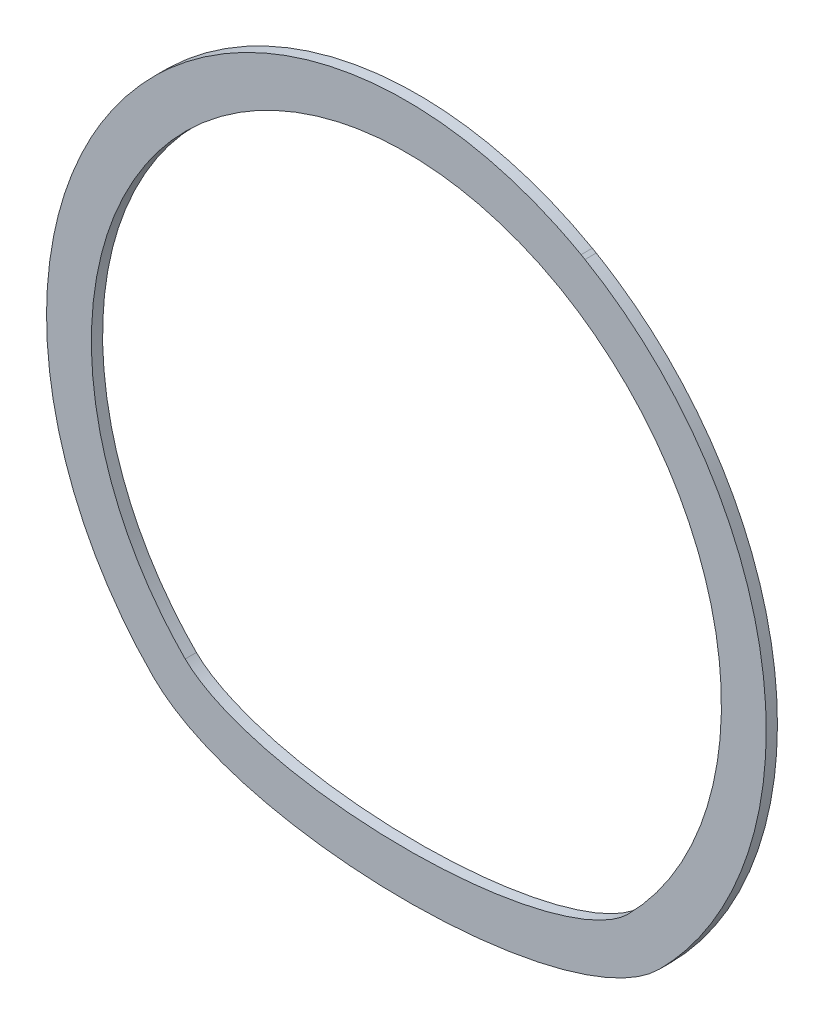
SolidWorks part; units mm, degrees
material "Balsa"
ref_plane "Front Plane" through (0, 0, 0) normal (0, 0, 1) x (1, 0, 0)
ref_plane "Top Plane" through (0, 0, 0) normal (0, 1, 0) x (1, 0, 0)
ref_plane "Right Plane" through (0, 0, 0) normal (1, 0, 0) x (0, 0, -1)
sketch "Sketch2" plane through (0, 0, 0) normal (0, 0, 1) x (1, 0, 0)
  spline S0 degree 3 poles (1916.9359, -3331.6619) (-3240.6007, 2836.854) (4021.1791, -1543.6671) (-3851.7215, 176.6002) knots -506.110745 -506.110745 -506.110745 -506.110745 508.578658 508.578658 508.578658 508.578658 only from (49.5009, 91.348) to (50.6103, 90.7129)
  spline S1 degree 3 poles (2660.8438, -2993.62) (-94.0194, -31.8616) (-51.8415, -94.056) (-74.4696, -70.0026) (-75.8372, -68.488) (-77.1861, -66.9319) (-78.5157, -65.3347) (-79.8244, -63.6962) (-81.5476, -61.4464) (-83.6416, -58.5297) (-85.6296, -55.5014) (-87.1622, -52.9973) (-88.2859, -51.0701) (-90.1147, -47.7724) (-92.5499, -42.8914) (-95.3516, -36.1752) (-97.8068, -28.8548) (-99.4166, -22.4927) (-100.4844, -16.9735) (-101.2174, -12.1158) (-101.8059, -6.1085) (-102.0556, 1.0556) (-101.6376, 11.9166) (-99.5817, 24.7034) (-94.9478, 39.4776) (-88.6565, 52.7081) (-80.0434, 65.5541) (-69.8712, 76.7554) (-58.637, 85.9148) (-47.202, 92.899) (-35.7905, 98.0522) (-24.0008, 101.7167) (-12.0295, 103.8942) (-3.6569, 104.3953) (0.9911, 104.3723) (2.6447, 104.3478) (5.2959, 104.2559) (8.9441, 104.0024) (12.9235, 103.5662) (16.8979, 102.9692) (20.8607, 102.2106) (24.805, 101.2899) (28.7242, 100.207) (32.6113, 98.9619) (36.4593, 97.5551) (39.9429, 96.1186) (42.4433, 94.9816) (43.9946, 94.2376) (44.9225, 93.7809) (45.8466, 93.3143) (46.7667, 92.8378) (47.6827, 92.3514) (68.8529, 80.8443) (140.5977, 30.98) (-3481.9654, 1968.9745) knots -0.290492 -0.290492 -0.290492 -0.290492 0.006795 0.013654 0.020575 0.02756 0.034609 0.041722 0.048899 0.063446 0.078252 0.085753 0.09332 0.100952 0.124124 0.148785 0.174948 0.202627 0.215494 0.232144 0.2526 0.276886 0.305032 0.363116 0.408011 0.462235 0.511576 0.564908 0.615598 0.658549 0.700916 0.742691 0.78387 0.82445 0.827809 0.831171 0.841279 0.854802 0.868378 0.882008 0.895692 0.909428 0.923217 0.93706 0.950955 0.964902 0.975398 0.978902 0.982411 0.985922 0.989437 0.992954 0.996476 1.243806 1.243806 1.243806 1.243806 only from (-71.6774, -72.9104) to (49.5009, 91.348)
  spline S2 degree 3 poles (-71.6774, -72.9104) (-72.1092, -72.4767) (-72.9729, -71.5936) (-74.4696, -70.0026) (-75.8372, -68.488) (-77.1861, -66.9319) (-78.5157, -65.3347) (-79.8244, -63.6962) (-81.5476, -61.4464) (-83.6416, -58.5297) (-85.6296, -55.5014) (-87.1622, -52.9973) (-88.2859, -51.0701) (-90.1147, -47.7724) (-92.5499, -42.8914) (-95.3516, -36.1752) (-97.8068, -28.8548) (-99.4166, -22.4927) (-100.4844, -16.9735) (-101.2174, -12.1158) (-101.8059, -6.1085) (-102.0556, 1.0556) (-101.6376, 11.9166) (-99.5817, 24.7034) (-94.9478, 39.4776) (-88.6565, 52.7081) (-80.0434, 65.5541) (-69.8712, 76.7554) (-58.637, 85.9148) (-47.202, 92.899) (-35.7905, 98.0522) (-24.0008, 101.7167) (-12.0295, 103.8942) (-3.6569, 104.3953) (0.9911, 104.3723) (2.6447, 104.3478) (5.2959, 104.2559) (8.9441, 104.0024) (12.9235, 103.5662) (16.8979, 102.9692) (20.8607, 102.2106) (24.805, 101.2899) (28.7242, 100.207) (32.6113, 98.9619) (36.4593, 97.5551) (39.9429, 96.1186) (42.4433, 94.9816) (43.9946, 94.2376) (44.9225, 93.7809) (45.8466, 93.3143) (46.7667, 92.8378) (47.6827, 92.3514) (48.5618, 91.8735) (49.1883, 91.5244) (49.5009, 91.348) knots 0 0 0 0 0.006795 0.013654 0.020575 0.02756 0.034609 0.041722 0.048899 0.063446 0.078252 0.085753 0.09332 0.100952 0.124124 0.148785 0.174948 0.202627 0.215494 0.232144 0.2526 0.276886 0.305032 0.363116 0.408011 0.462235 0.511576 0.564908 0.615598 0.658549 0.700916 0.742691 0.78387 0.82445 0.827809 0.831171 0.841279 0.854802 0.868378 0.882008 0.895692 0.909428 0.923217 0.93706 0.950955 0.964902 0.975398 0.978902 0.982411 0.985922 0.989437 0.992954 0.996476 1 1 1 1
  spline S3 degree 3 poles (49.5009, 91.348) (49.872, 91.1385) (50.2418, 90.9268) (50.6103, 90.7129) knots 0 0 0 0 1 1 1 1
  spline S4 degree 3 poles (-3346.3837, 2202.0383) (73.8317, 60.8817) (25.255, 106.4505) (53.9325, 88.7036) (55.5798, 87.6387) (57.2181, 86.5331) (58.847, 85.3874) (60.4652, 84.2011) (62.6149, 82.559) (65.2687, 80.4032) (68.3802, 77.661) (71.4204, 74.7537) (74.3792, 71.6812) (77.2464, 68.4441) (79.5428, 65.6199) (81.3243, 63.2803) (82.6352, 61.4798) (83.9151, 59.6395) (85.6826, 56.9767) (87.8969, 53.3695) (90.4626, 48.6769) (92.8892, 43.6261) (95.1327, 38.2157) (97.1465, 32.4482) (98.8821, 26.3306) (100.2892, 19.8751) (101.2586, 13.4739) (101.8173, 7.2467) (102.0152, 1.305) (101.8786, -4.6242) (101.3926, -10.7347) (100.5371, -16.8676) (99.3294, -22.8638) (97.8936, -28.3722) (96.657, -32.2698) (95.7856, -34.7444) (95.046, -36.7643) (93.9532, -39.5358) (92.4358, -43.007) (90.8217, -46.3649) (89.1186, -49.6082) (87.3342, -52.7363) (85.4757, -55.7486) (83.5505, -58.6453) (81.5655, -61.4266) (79.3077, -64.3807) (77.437, -66.6472) (76.0073, -68.2889) (75.2951, -69.0897) (74.579, -69.8782) (73.8594, -70.6545) (73.1363, -71.4184) (60.0474, -84.947) (112.6093, -25.8248) (-2703.3653, -2952.5697) knots -0.468149 -0.468149 -0.468149 -0.468149 0.010157 0.020393 0.030709 0.041103 0.051576 0.062128 0.072758 0.094254 0.116062 0.138181 0.16061 0.183347 0.206391 0.218027 0.22974 0.241529 0.253393 0.280162 0.30828 0.337739 0.36853 0.400644 0.434071 0.4688 0.504821 0.536145 0.567394 0.59857 0.62967 0.664059 0.696204 0.726123 0.75383 0.760691 0.767516 0.787768 0.807688 0.827278 0.84654 0.865477 0.884089 0.902378 0.920346 0.937994 0.961032 0.966703 0.97234 0.977942 0.983508 0.98904 0.994538 1.247123 1.247123 1.247123 1.247123 only from (50.6103, 90.7129) to (71.6784, -72.9104)
  spline S5 degree 3 poles (50.6103, 90.7129) (51.1284, 90.4118) (52.1672, 89.796) (53.9325, 88.7036) (55.5798, 87.6387) (57.2181, 86.5331) (58.847, 85.3874) (60.4652, 84.2011) (62.6149, 82.559) (65.2687, 80.4032) (68.3802, 77.661) (71.4204, 74.7537) (74.3792, 71.6812) (77.2464, 68.4441) (79.5428, 65.6199) (81.3243, 63.2803) (82.6352, 61.4798) (83.9151, 59.6395) (85.6826, 56.9767) (87.8969, 53.3695) (90.4626, 48.6769) (92.8892, 43.6261) (95.1327, 38.2157) (97.1465, 32.4482) (98.8821, 26.3306) (100.2892, 19.8751) (101.2586, 13.4739) (101.8173, 7.2467) (102.0152, 1.305) (101.8786, -4.6242) (101.3926, -10.7347) (100.5371, -16.8676) (99.3294, -22.8638) (97.8936, -28.3722) (96.657, -32.2698) (95.7856, -34.7444) (95.046, -36.7643) (93.9532, -39.5358) (92.4358, -43.007) (90.8217, -46.3649) (89.1186, -49.6082) (87.3342, -52.7363) (85.4757, -55.7486) (83.5505, -58.6453) (81.5655, -61.4266) (79.3077, -64.3807) (77.437, -66.6472) (76.0073, -68.2889) (75.2951, -69.0897) (74.579, -69.8782) (73.8594, -70.6545) (73.1363, -71.4184) (72.3175, -72.2647) (71.8912, -72.6967) (71.6784, -72.9104) knots 0 0 0 0 0.010157 0.020393 0.030709 0.041103 0.051576 0.062128 0.072758 0.094254 0.116062 0.138181 0.16061 0.183347 0.206391 0.218027 0.22974 0.241529 0.253393 0.280162 0.30828 0.337739 0.36853 0.400644 0.434071 0.4688 0.504821 0.536145 0.567394 0.59857 0.62967 0.664059 0.696204 0.726123 0.75383 0.760691 0.767516 0.787768 0.807688 0.827278 0.84654 0.865477 0.884089 0.902378 0.920346 0.937994 0.961032 0.966703 0.97234 0.977942 0.983508 0.98904 0.994538 1 1 1 1
  spline S6 degree 3 poles (-3842.8721, 688.3174) (4597.8502, -352.084) (-4597.8455, -352.0843) (3842.8638, 688.3162) knots -2.698057 -2.698057 -2.698057 -2.698057 3.698055 3.698055 3.698055 3.698055 weights 1 1 1 1 only from (71.6784, -72.9104) to (-71.6774, -72.9104)
  spline S7 degree 3 poles (71.6784, -72.9104) (46.3599, -98.3417) (-46.3589, -98.3417) (-71.6774, -72.9104) knots 0 0 0 0 1 1 1 1 weights 1 1 1 1
  spline S8 degree 1 poles (-62.6772, -63.9502) (43.2582, 80.2883) knots 0 0 1 1 construction
  spline S9 degree 1 poles (43.2582, 80.2883) (44.2327, 79.7303) knots 0 0 1 1 construction
  spline S10 degree 1 poles (44.2327, 79.7303) (62.6782, -63.9502) knots 0 0 1 1 construction
  spline S11 degree 1 poles (62.6782, -63.9502) (-62.6772, -63.9502) knots 0 0 1 1 construction
  spline S12 degree 3 poles (-62.6772, -63.9502) (-62.8955, -63.7309) (-63.3217, -63.2983) (-64.0021, -62.5921) (-64.7538, -61.7946) (-65.7039, -60.7646) (-66.8046, -59.5274) (-68.5568, -57.4681) (-70.6482, -54.8355) (-73.8114, -50.469) (-77.3945, -44.7561) (-82.3029, -35.1354) (-86.8108, -22.36) (-90.3543, -0.9674) (-87.6499, 26.3501) (-73.3334, 55.9721) (-49.624, 78.7088) (-24.4872, 89.3835) (-3.091, 92.1159) (13.039, 91.1975) (26.1203, 87.9966) (34.8794, 84.5248) (39.1021, 82.5104) (41.2143, 81.4108) (42.347, 80.7976) (42.9592, 80.4569) (43.2582, 80.2883) knots 0 0 0 0 0.003906 0.007812 0.011719 0.015625 0.023437 0.03125 0.046875 0.062499 0.093749 0.124999 0.187498 0.249998 0.374997 0.499996 0.624995 0.749994 0.812493 0.874993 0.937492 0.968742 0.984367 0.992179 0.996085 0.999992 0.999992 0.999992 0.999992
  spline S13 degree 3 poles (43.2582, 80.2883) (43.3397, 80.2423) (43.5025, 80.15) (43.7464, 80.0108) (43.9898, 79.871) (44.1518, 79.7773) (44.2327, 79.7303) knots 0.002022 0.002022 0.002022 0.002022 0.251014 0.500005 0.748996 0.997987 0.997987 0.997987 0.997987
  spline S14 degree 3 poles (44.2327, 79.7303) (44.5844, 79.526) (45.2596, 79.1276) (46.4154, 78.4223) (47.5738, 77.6928) (49.0079, 76.7584) (50.8048, 75.5306) (53.6072, 73.4932) (57.0034, 70.7903) (64.7641, 63.8421) (74.8536, 51.7693) (84.3118, 33.0007) (89.3026, 12.5818) (89.5941, -8.4639) (85.1673, -29.0225) (78.4712, -43.2887) (72.7378, -52.0045) (70.1455, -55.4923) (67.9548, -58.1887) (66.5372, -59.8344) (65.3768, -61.1241) (64.6361, -61.9238) (64.0489, -62.544) (63.5408, -63.0721) (63.0657, -63.5594) (62.8132, -63.8146) (62.6782, -63.9502) knots 0.000015 0.000015 0.000015 0.000015 0.007827 0.015639 0.023452 0.031264 0.046889 0.062514 0.093763 0.125013 0.250011 0.375009 0.500007 0.625005 0.750004 0.875002 0.906251 0.937501 0.953126 0.96875 0.976563 0.984375 0.988281 0.992188 0.996094 1 1 1 1
  spline S15 degree 3 poles (62.6782, -63.9502) (62.4421, -64.1873) (61.9735, -64.6322) (60.8483, -65.5949) (59.1789, -66.8259) (56.7375, -68.3252) (52.9423, -70.2888) (47.261, -72.5995) (39.2215, -74.978) (30.229, -76.8801) (17.3048, -78.7217) (0.0005, -79.6587) (-17.3038, -78.7217) (-30.228, -76.8801) (-39.2204, -74.978) (-47.2599, -72.5995) (-52.9413, -70.2888) (-56.7364, -68.3252) (-59.1779, -66.8259) (-60.8473, -65.5949) (-61.9724, -64.6322) (-62.4411, -64.1873) (-62.6772, -63.9502) knots 0 0 0 0 0.015625 0.03125 0.0625 0.09375 0.125 0.1875 0.25 0.3125 0.375 0.5 0.625 0.6875 0.75 0.8125 0.875 0.90625 0.9375 0.96875 0.984375 1 1 1 1
  dimension "D1" = 12.7
extrude "Boss-Extrude1" add sketch "Sketch2" against normal blind 3.175
